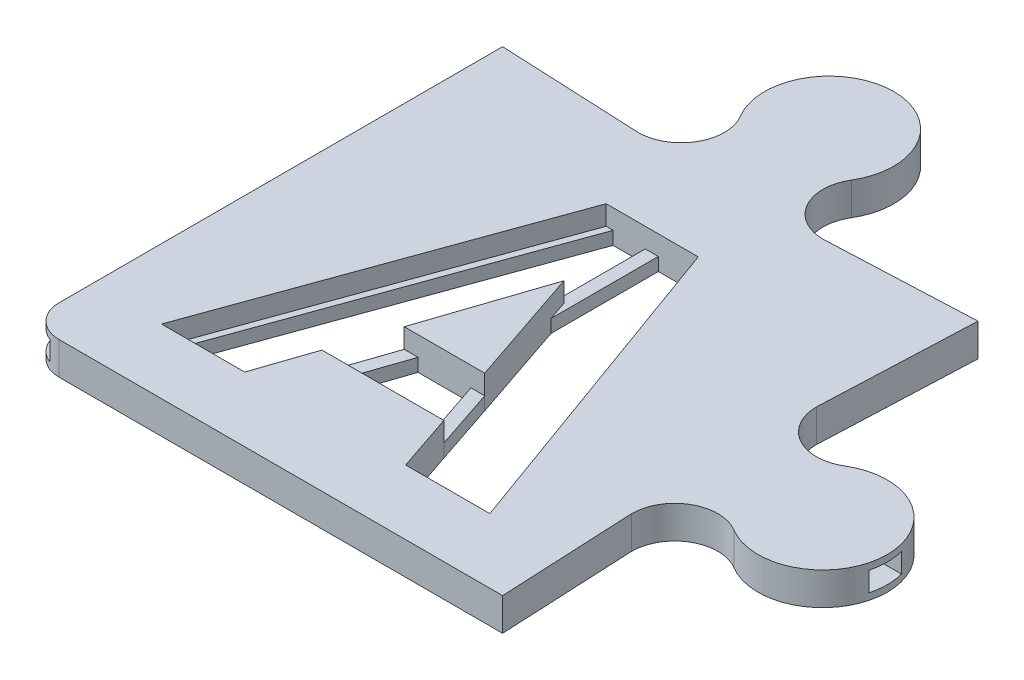
SolidWorks part; units mm, degrees
ref_plane "Front Plane" through (0, 0, 0) normal (0, 0, 1) x (1, 0, 0)
ref_plane "Top Plane" through (0, 0, 0) normal (0, 1, 0) x (1, 0, 0)
ref_plane "Right Plane" through (0, 0, 0) normal (1, 0, 0) x (0, 0, -1)
sketch "Sketch1" plane through (0, 0, 0) normal (0, 1, 0) x (1, 0, 0)
  line L0 (-31, -36) -> (37, -36) construction
  line L1 (-36, 37) -> (-36, -31) construction
  line L2 (-14.1421, 36) -> (-36, 37) construction
  line L3 (37, 37) -> (14.1421, 36) construction
  line L4 (36, 13.1421) -> (37, 37) construction
  line L5 (37, -36) -> (36, -15.1421) construction
  line L6 (-35.9, 36.8953) -> (-35.9, -31)
  line L7 (-36, 36) -> (36, 36) construction
  line L8 (-36, 36) -> (-36, -36) construction
  line L9 (-36, -36) -> (36, -36) construction
  line L10 (36, 36) -> (36, -36) construction
  line L11 (-31, -35.9) -> (36.8951, -35.9)
  line L12 (36.8951, -35.9) -> (35.9, -15.1445)
  line L13 (35.9, 13.1442) -> (36.8955, 36.8953)
  line L14 (36.8955, 36.8953) -> (14.1443, 35.9)
  line L15 (-14.1444, 35.9) -> (-35.9, 36.8953)
  line L16 (-30, -24) -> (30, -24) construction
  line L17 (-30, 29) -> (30, 29) construction
  line L18 (-30, 29) -> (-30, -31) construction
  line L19 (-30, -31) -> (30, -31) construction
  line L20 (30, 29) -> (30, -31) construction
  line L21 (-30, 24) -> (30, 24) construction
  line L22 (-30, 24) -> (-30, -26) construction
  line L23 (-30, -26) -> (30, -26) construction
  line L24 (30, 24) -> (30, -26) construction
  arc A0 (-36, -31) -> (-31, -36) centre (-31, -31) ccw construction
  arc A1 (-14.1421, 36) -> (-8.571, 45.8485) centre (-14.1421, 42.5) ccw construction
  arc A2 (8.571, 45.8485) -> (-8.571, 45.8485) centre (0, 51) ccw construction
  arc A3 (8.571, 45.8485) -> (14.1421, 36) centre (14.1421, 42.5) ccw construction
  arc A4 (36, 13.1421) -> (45.8485, 7.571) centre (42.5, 13.1421) ccw construction
  arc A5 (45.8485, -9.571) -> (45.8485, 7.571) centre (51, -1) ccw construction
  arc A6 (45.8485, -9.571) -> (36, -15.1421) centre (42.5, -15.1421) ccw construction
  arc A7 (-35.9, -31) -> (-31, -35.9) centre (-31, -31) ccw
  arc A8 (45.9, -9.4853) -> (35.9, -15.1445) centre (42.5, -15.1421) ccw
  arc A9 (45.9, -9.4853) -> (45.9, 7.4853) centre (51, -1) ccw
  arc A10 (35.9, 13.1442) -> (45.9, 7.4853) centre (42.5, 13.1421) ccw
  arc A11 (8.4853, 45.9) -> (14.1443, 35.9) centre (14.1421, 42.5) ccw
  arc A12 (8.4853, 45.9) -> (-8.4853, 45.9) centre (0, 51) ccw
  arc A13 (-14.1444, 35.9) -> (-8.4853, 45.9) centre (-14.1421, 42.5) ccw
  point P32 (36, 0)
  point P34 (0, 36)
  dimension "D5" = 6.5
  dimension "D6" = 10
  dimension "D7" = 6.5
  dimension "D13" = 5
  dimension "D9" = 10
  dimension "D11" = 6.5
  dimension "D12" = 6.5
  dimension "D1" = 72
  dimension "D2" = 1
  dimension "D3" = 1
  dimension "D4" = 15
  dimension "D8" = 1
  dimension "D10" = 35
  dimension "D14" = 15
  dimension "D15" = 36
  dimension "D16" = 1
  dimension "D18" = 60
  dimension "D19" = 60
  dimension "D20" = 5
  dimension "D21" = 6
  dimension "D22" = 5
  dimension "D23" = 50
  dimension "D24" = 2
  dimension "D17" = 0.1
extrude "Boss-Extrude1" add sketch "Sketch1" along normal blind 5
sketch "Sketch3" plane through (0, 5, 0) normal (0, 1, 0) x (1, 0, 0)
  text T0 "A" font "Poppins" height 50
extrude "Cut-Extrude1" cut sketch "Sketch3" against normal blind 3
sketch "Sketch4" plane through (0, 2, 0) normal (0, 1, 0) x (1, 0, 0)
  line L0 (-0.1649, 10.5416) -> (-0.1649, 24) construction
  line L1 (-30, 24) -> (30, 24) construction
  line L2 (-0.1649, 10.5416) -> (-6.2964, -7.7704) construction
  line L3 (-1.1599, 7.5701) -> (0.8401, 7.5701)
  line L4 (-1.1599, 7.5701) -> (-1.1599, 24)
  line L5 (-1.1599, 24) -> (0.8401, 24)
  line L6 (0.8401, 7.5701) -> (0.8401, 24)
  line L7 (6.0284, -7.7704) -> (-0.1649, 10.5416) construction
  line L8 (-9.5012, -17.1686) -> (-6.2964, -7.7704)
  line L9 (-6.2964, -7.7704) -> (-4.1833, -7.7704)
  line L10 (-6.2964, -7.7704) -> (6.0284, -7.7704) construction
  line L11 (-4.1833, -7.7704) -> (-7.3881, -17.1686)
  line L12 (9.1612, -17.1686) -> (-9.5012, -17.1686) construction
  line L13 (-7.3881, -17.1686) -> (-9.5012, -17.1686)
  line L14 (6.0284, -7.7704) -> (9.1612, -17.1686)
  line L15 (9.1612, -17.1686) -> (7.053, -17.1686)
  line L16 (9.1612, -17.1686) -> (-9.5012, -17.1686) construction
  line L17 (7.053, -17.1686) -> (3.9203, -7.7704)
  line L18 (-6.2964, -7.7704) -> (6.0284, -7.7704) construction
  line L19 (3.9203, -7.7704) -> (6.0284, -7.7704)
  line L20 (-6.0883, 24) -> (-24.1736, -26)
  line L21 (-30, -26) -> (30, -26) construction
  line L22 (5.8925, 24) -> (23.9778, -26)
  line L23 (6.9559, 24) -> (25.0412, -26) construction
  line L24 (-25.237, -26) -> (-7.1517, 24) construction
  line L25 (-25.237, -26) -> (-7.1517, 24) construction
  line M14 (-6.2964, -7.7704) -> (-0.1649, 10.5416)
  line M15 (-0.1649, 10.5416) -> (6.0284, -7.7704)
  line M16 (6.0284, -7.7704) -> (-6.2964, -7.7704)
  line M17 (9.1612, -17.1686) -> (12.1496, -26)
  line M18 (12.1496, -26) -> (25.0412, -26)
  line M19 (25.0412, -26) -> (6.9559, 24)
  line M20 (6.9559, 24) -> (-7.1517, 24)
  line M21 (-7.1517, 24) -> (-25.237, -26)
  line M22 (-25.237, -26) -> (-12.4897, -26)
  line M23 (-12.4897, -26) -> (-9.5012, -17.1686)
  line M24 (-9.5012, -17.1686) -> (9.1612, -17.1686)
  dimension "D1" = 2
  dimension "D2" = 2
  dimension "D3" = 2
  dimension "D4" = 1
  dimension "D5" = 1
extrude "Cut-Extrude2" cut sketch "Sketch4" against normal through all contours L17 L11 M24 M16 | L14 L6 M15 M17 M18 M19 M20 | L8 L4 M23 M14 M20 M21 M22 region at (-10.681, 2, 3.2498) region at (10.4215, 2, 3.228) region at (-0.1512, 2, 12.9098)
sketch "Sketch6" plane through (0, 0, 0) normal (0, -1, 0) x (1, 0, 0)
  line L0 (-35.9, -36.8953) -> (-35.9, 31) construction
  line L1 (-35.9, 18.9) -> (-27.9, 18.9)
  line L2 (-35.9, 18.9) -> (-35.9, -15.1)
  line L3 (-35.9, -15.1) -> (-27.9, -15.1)
  line L4 (-27.9, 18.9) -> (-27.9, -15.1)
  line L5 (-31, 35.9) -> (36.8951, 35.9) construction
  line L6 (-35.9, 15.65) -> (-30.9, 15.65)
  line L7 (-35.9, 15.65) -> (-35.9, -11.85)
  line L8 (-35.9, -11.85) -> (-30.9, -11.85)
  line L9 (-30.9, 15.65) -> (-30.9, -11.85)
  point P15 (-27.9, 1.9)
  point P16 (-30.9, 1.9)
  line M28 (-35.9, 31) -> (-35.9, -36.8953)
  dimension "D1" = 8
  dimension "D2" = 20.25
  dimension "D3" = 27.5
  dimension "D4" = 5
  dimension "D5" = 34
extrude "Cut-Extrude3" cut sketch "Sketch6" against normal blind 3 from offset 1 contours L6 L9 L8 L3 L4 L1 M28 | L9 L6 L2 L8 region at (-30.3665, 0, 1.9) region at (-33.4, 0, 1.9) offset against normal yes
extrude "Cut-Extrude4" cut sketch "Sketch6<3>" against normal up to next contours L9 L6 L2 L8 region at (-33.4, 0, 1.9)
sketch "Sketch6<3>" plane through (0, 0, 0) normal (0, -1, 0) x (1, 0, 0) same geometry as "Sketch6"
sketch "Sketch8" plane through (0, 0, 0) normal (0, -1, 0) x (1, 0, 0)
  line L1 (-2.5, -51.9) -> (2.5, -51.9)
  line L2 (-2.5, -51.9) -> (-2.5, -60.9)
  line L3 (-2.5, -60.9) -> (2.5, -60.9)
  line L4 (2.5, -51.9) -> (2.5, -60.9)
  line L5 (51.9, 3.5) -> (60.9, 3.5)
  line L6 (51.9, 3.5) -> (51.9, -1.5)
  line L7 (51.9, -1.5) -> (60.9, -1.5)
  line L8 (60.9, 3.5) -> (60.9, -1.5)
  arc A0 (-8.4853, -45.9) -> (8.4853, -45.9) centre (0, -51) ccw construction
  arc A1 (45.9, -7.4853) -> (45.9, 9.4853) centre (51, 1) ccw construction
  point P4 (0, -60.9)
  point P13 (60.9, 1)
  dimension "D1" = 5
  dimension "D2" = 9
  dimension "D3" = 5
  dimension "D4" = 9
extrude "Cut-Extrude5" cut sketch "Sketch8" against normal blind 3 from offset 1 offset against normal yes
sketch "Sketch9" plane through (0, 0, 0) normal (0, -1, 0) x (1, 0, 0)
  line L0 (-31, 35.9) -> (36.8951, 35.9) construction
  line L1 (-35.9, 15.65) -> (-35.9, 31) construction
  line L2 (-32.6347, 35.6193) -> (-35.9, 31) construction
  line L3 (-33.5931, 30.1085) -> (-30.7069, 34.1915) construction
  line L4 (-30.7069, 34.1915) -> (-33.5931, 30.1085) construction
  line L5 (-30.7069, 34.1915) -> (-33.3993, 36.0946)
  line L6 (-33.5931, 30.1085) -> (-36.2854, 32.0117)
  line L7 (-33.3993, 36.0946) -> (-36.2854, 32.0117)
  circle A0 centre (-32.15, 32.15) radius 2.5
  arc A1 (-31, 35.9) -> (-35.9, 31) centre (-31, 31) ccw construction
  arc M41 (-31, 35.9) -> (-35.9, 31) centre (-31, 31) ccw
  dimension "D1" = 5
  dimension "D3" = 3.75
  dimension "D4" = 5.6569
  dimension "D2" = 3.75
extrude "Cut-Extrude6" cut sketch "Sketch9" against normal blind 3 from offset 1 contours A0 L5 L6 M41 | A0 L5 region at (-34.2529, 0, 33.6365) region at (-32.15, 0, 32.15) offset against normal yes
